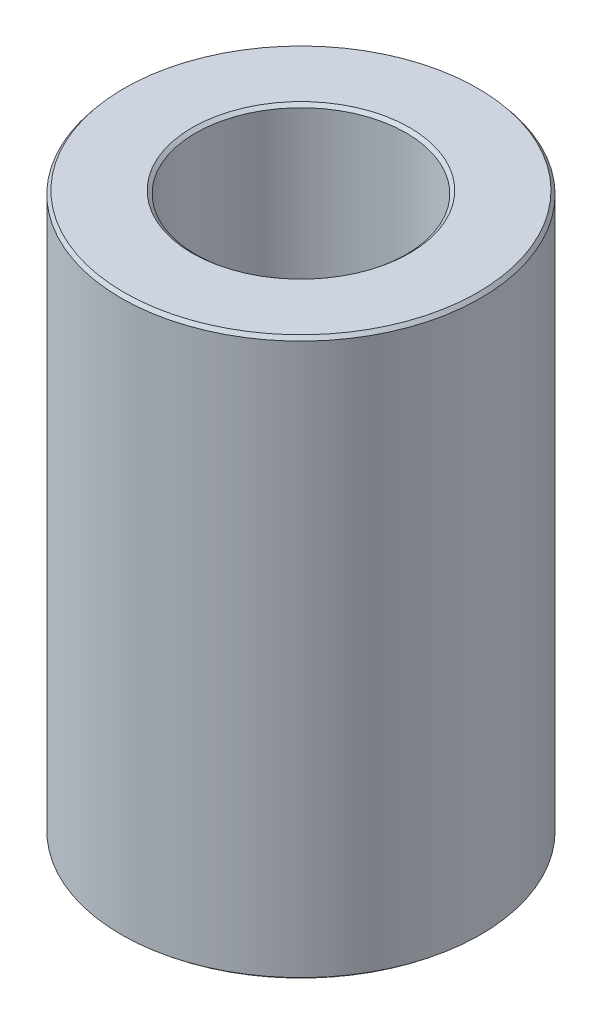
SolidWorks part; units mm, degrees
ref_plane "Front Plane" through (0, 0, 0) normal (0, 0, 1) x (1, 0, 0)
ref_plane "Top Plane" through (0, 0, 0) normal (0, 1, 0) x (1, 0, 0)
ref_plane "Right Plane" through (0, 0, 0) normal (1, 0, 0) x (0, 0, -1)
sketch "Sketch1" plane through (0, 0, 0) normal (0, 1, 0) x (1, 0, 0)
  circle A0 centre (0, 0) radius 57.5
  dimension "SLEEVE_OD" = 115
extrude "Boss-Extrude1" add sketch "Sketch1" along normal blind 178.4118
sketch "Sketch2" plane through (0, 0, 0) normal (0, 1, 0) x (1, 0, 0)
  circle A0 centre (0, 0) radius 33.6863
  dimension "BORE_D" = 67.3726
extrude "Cut-Extrude1" cut sketch "Sketch2" along normal through all
chamfer "Chamfer1" distance 1.1224 angle 39.379 4 edges at (0, 178.4118, 33.6863) (0, 0, 33.6863) (0, 0, 57.5) (0, 178.4118, 57.5) first distance on face at (0, 178.4118, 33.6863) first distance on face at (0, 0, 33.6863) first distance on face at (0, 178.4118, 57.5)
